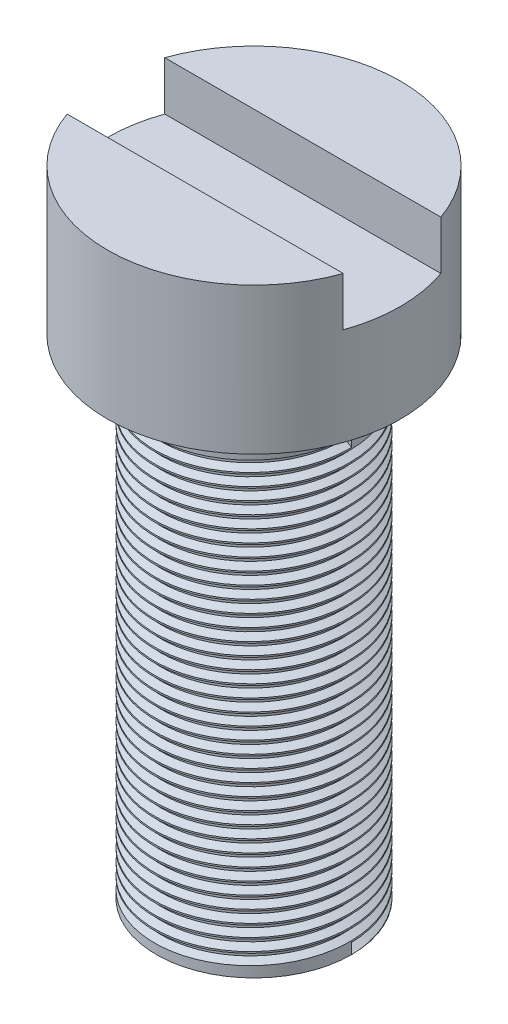
SolidWorks part; units mm, degrees
ref_plane "Front Plane" through (0, 0, 0) normal (0, 0, 1) x (1, 0, 0)
ref_plane "Top Plane" through (0, 0, 0) normal (0, 1, 0) x (1, 0, 0)
ref_plane "Right Plane" through (0, 0, 0) normal (1, 0, 0) x (0, 0, -1)
sketch "Sketch1" plane through (0, 0, 0) normal (0, 1, 0) x (1, 0, 0)
  circle A1 centre (0, 0) radius 15
  dimension "D1" = 30
extrude "Boss-Extrude1" add sketch "Sketch1" along normal mid plane 15
sketch "Sketch2" plane through (0, 0, 0) normal (1, 0, 0) x (0, 0, -1)
  line L0 (15, 7.5) -> (-15, 7.5) construction
  line L1 (-5, 2.5) -> (5, 2.5)
  line L2 (-5, 2.5) -> (-5, 7.5)
  line L3 (-5, 7.5) -> (5, 7.5)
  line L4 (5, 2.5) -> (5, 7.5)
  line L5 (-5, 2.5) -> (5, 7.5) construction
  line L6 (-5, 7.5) -> (5, 2.5) construction
  point P0 (0, 5)
  dimension "D1" = 5
  dimension "D2" = 10
extrude "Cut-Extrude1" cut sketch "Sketch2" against normal mid plane 45
sketch "Sketch3" plane through (0, -7.5, 0) normal (0, -1, 0) x (1, 0, 0)
  circle A0 centre (0, 0) radius 10
  dimension "D1" = 20
extrude "Boss-Extrude2" add sketch "Sketch3" along normal blind 50
thread "Thread1" pitch 1.25 method cut profile "Thread Profile1" start angle 0, offset 0, length 45, pitch 1.25, diameter 20
ref_plane "Plane1" through (10, -57.5, 0) normal (0, 0, 1) x (1, 0, 0)
sketch "Thread Profile1" plane through (10, -57.5, 0) normal (0, 0, 1) x (1, 0, 0)
  line L0 (0, 0) -> (0, 1.25) construction
  line L11 (0, 0) -> (0, 1.0937)
  line L12 (0, 1.0937) -> (-0.6766, 0.7031)
  line L13 (-0.6766, 0.7031) -> (-0.6766, 0.3906)
  line L15 (-0.6766, 0.3906) -> (0, 0)
  line L17 (-0.6766, 0.5469) -> (0, 0.5469) construction
  point P2 (0, 0)
  dimension "Pitch" = 1.25
  dimension "Profile_Angle" = 60
  dimension "Profile_Land" = 0.3125
  dimension "Profile_Height" = 0.6766
